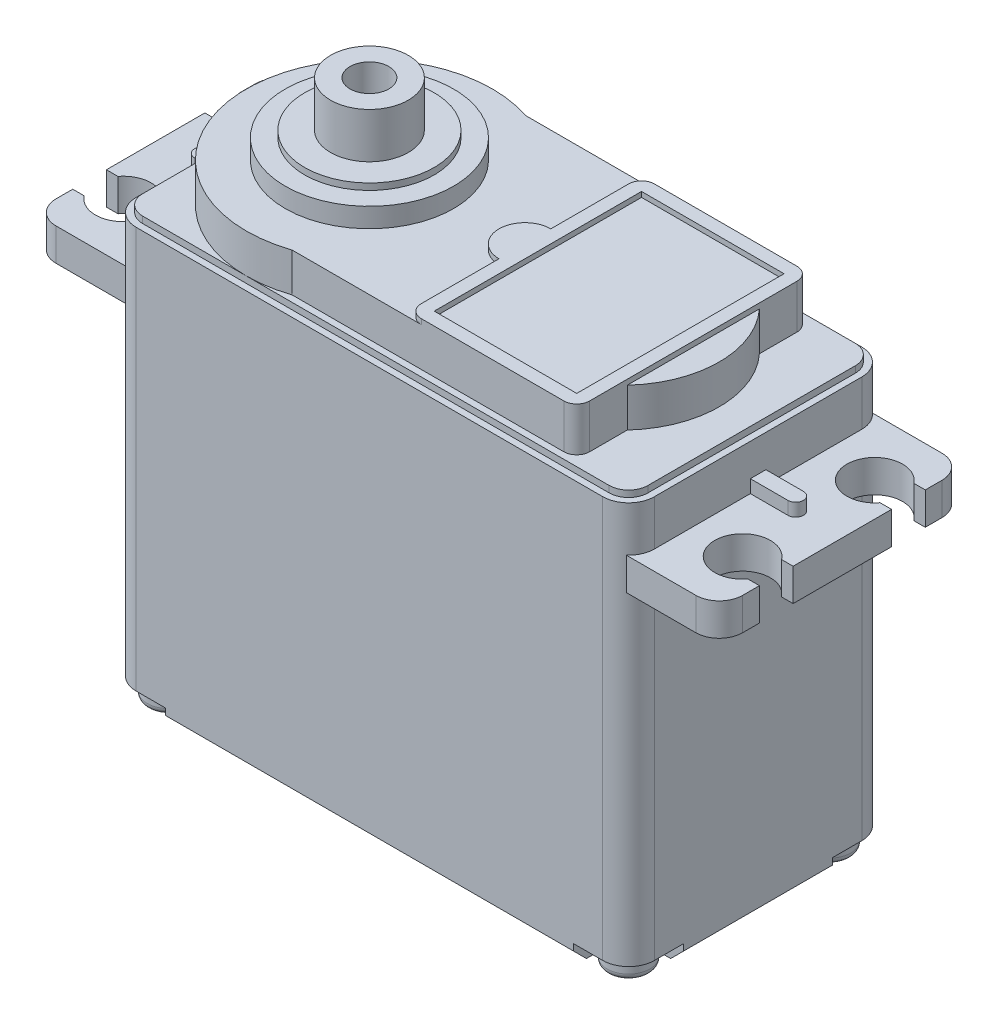
SolidWorks part; units mm, degrees
ref_plane "Спереди" through (0, 0, 0) normal (0, 0, 1) x (1, 0, 0)
ref_plane "Сверху" through (0, 0, 0) normal (0, 1, 0) x (1, 0, 0)
ref_plane "Справа" through (0, 0, 0) normal (1, 0, 0) x (0, 0, -1)
sketch "Эскиз1" plane through (0, 0, 0) normal (0, 1, 0) x (1, 0, 0)
  line L1 (-18, -10) -> (18, -10)
  line L2 (-20, -8) -> (-20, 8)
  line L3 (-18, 10) -> (18, 10)
  line L4 (20, -8) -> (20, 8)
  line L5 (-20, -10) -> (20, 10) construction
  line L6 (-20, 10) -> (20, -10) construction
  arc A0 (-18, -10) -> (-20, -8) centre (-18, -8) cw
  arc A1 (20, -8) -> (18, -10) centre (18, -8) cw
  arc A2 (20, 8) -> (18, 10) centre (18, 8) ccw
  arc A3 (-20, 8) -> (-18, 10) centre (-18, 8) cw
  point P0 (0, 0)
  dimension "D3" = 2
  dimension "D1" = 20
  dimension "D2" = 40
extrude "Бобышка-Вытянуть1" add sketch "Эскиз1" along normal blind 32.5
sketch "Эскиз2" plane through (0, 32.5, 0) normal (0, 1, 0) x (1, 0, 0)
  line L12 (-18, -9.5) -> (18, -9.5)
  line L13 (19.5, -8) -> (19.5, 8)
  line L14 (18, 9.5) -> (-18, 9.5)
  line L15 (-19.5, 8) -> (-19.5, -8)
  line L16 (-18, -9.5) -> (18, -9.5)
  line L17 (19.5, -8) -> (19.5, 8)
  line L18 (18, 9.5) -> (-18, 9.5)
  line L19 (-19.5, 8) -> (-19.5, -8)
  arc A10 (-19.5, -8) -> (-18, -9.5) centre (-18, -8) ccw
  arc A11 (18, -9.5) -> (19.5, -8) centre (18, -8) ccw
  arc A12 (19.5, 8) -> (18, 9.5) centre (18, 8) ccw
  arc A13 (-18, 9.5) -> (-19.5, 8) centre (-18, 8) ccw
  arc A14 (-19.5, -8) -> (-18, -9.5) centre (-18, -8) ccw
  arc A15 (18, -9.5) -> (19.5, -8) centre (18, -8) ccw
  arc A16 (19.5, 8) -> (18, 9.5) centre (18, 8) ccw
  arc A17 (-18, 9.5) -> (-19.5, 8) centre (-18, 8) ccw
  dimension "D1" = 0.5
extrude "Бобышка-Вытянуть2" add sketch "Эскиз2" along normal blind 0.5
sketch "Эскиз3" plane through (0, 0, 0) normal (0, -1, 0) x (1, 0, 0)
  line L0 (-21.9185, 5.75) -> (-17.75, 5.75)
  line L1 (-15.75, 7.75) -> (-15.75, 12.0926)
  line L2 (-20, -8) -> (-20, 8) construction
  line L3 (-18, 10) -> (18, 10) construction
  line L4 (-21.9185, 5.75) -> (-21.9185, 12.0926)
  line L6 (-15.75, 12.0926) -> (-21.9185, 12.0926)
  line L8 (15.75, 12.0926) -> (21.9185, 12.0926)
  line L9 (21.9185, 5.75) -> (21.9185, 12.0926)
  line L10 (15.75, 7.75) -> (15.75, 12.0926)
  line L11 (21.9185, 5.75) -> (17.75, 5.75)
  line L12 (21.9185, -5.75) -> (17.75, -5.75)
  line L13 (15.75, -7.75) -> (15.75, -12.0926)
  line L14 (21.9185, -5.75) -> (21.9185, -12.0926)
  line L15 (15.75, -12.0926) -> (21.9185, -12.0926)
  line L16 (-15.75, -12.0926) -> (-21.9185, -12.0926)
  line L17 (-21.9185, -5.75) -> (-21.9185, -12.0926)
  line L18 (-15.75, -7.75) -> (-15.75, -12.0926)
  line L19 (-21.9185, -5.75) -> (-17.75, -5.75)
  arc A0 (-15.75, 7.75) -> (-17.75, 5.75) centre (-17.75, 7.75) cw
  arc A1 (15.75, 7.75) -> (17.75, 5.75) centre (17.75, 7.75) ccw
  arc A2 (15.75, -7.75) -> (17.75, -5.75) centre (17.75, -7.75) cw
  arc A3 (-15.75, -7.75) -> (-17.75, -5.75) centre (-17.75, -7.75) ccw
  point P11 (-15.75, 5.75)
  point P21 (15.75, 5.75)
  point P34 (15.75, -5.75)
  point P35 (-15.75, -5.75)
  dimension "D3" = 2
  dimension "D1" = 4.25
  dimension "D2" = 4.25
extrude "Вырез-Вытянуть1" cut sketch "Эскиз3" against normal blind 1.5
chamfer "Фаска1" distance 1 angle 45 4 edges at (20, 0, 0) (0, 0, -10) (-20, 0, 0) (0, 0, 10)
sketch "Эскиз4" plane through (0, 33, 0) normal (0, 1, 0) x (1, 0, 0)
  line L1 (18, 9.5) -> (-18, 9.5) construction
  line L2 (-18, -9.5) -> (18, -9.5) construction
  line L3 (-19.5, 8) -> (-19.5, -8) construction
  line L4 (15, 8) -> (15, -8)
  line L5 (20, -8) -> (20, 8) construction
  line L6 (-6.9586, 9) -> (14, 9)
  line L7 (-6.9586, -9) -> (14, -9)
  line L8 (18, 10) -> (-18, 10) construction
  line L9 (-18, -10) -> (18, -10) construction
  arc A0 (-6.9586, 9) -> (-6.9586, -9) centre (-10, 0) ccw
  arc A1 (15, 8) -> (14, 9) centre (14, 8) ccw
  arc A2 (15, -8) -> (14, -9) centre (14, -8) cw
  dimension "D1" = 5
  dimension "D4" = 1
  dimension "D2" = 1
  dimension "D3" = 1
extrude "Бобышка-Вытянуть3" add sketch "Эскиз4" along normal blind 3
sketch "Эскиз5" plane through (0, 36, 0) normal (0, 1, 0) x (1, 0, 0)
  line L0 (15, -8) -> (15, 8) construction
  line L1 (15, -8) -> (15, 8)
  line L2 (2, 8) -> (2, 2)
  line L3 (14, 9) -> (3, 9)
  line L4 (2, -2) -> (2, -8)
  line L5 (14, -9) -> (3, -9)
  line L6 (3, -8) -> (14, -8)
  line L7 (14, 8) -> (3, 8)
  line L8 (3, 8) -> (3, -8)
  line L9 (14, -8) -> (14, 8)
  line L11 (2, 8) -> (2, -8) construction
  arc A0 (15, 8) -> (14, 9) centre (14, 8) ccw construction
  arc A1 (14, -9) -> (15, -8) centre (14, -8) ccw construction
  arc A2 (15, 8) -> (14, 9) centre (14, 8) ccw
  arc A3 (14, -9) -> (15, -8) centre (14, -8) ccw
  arc A4 (3, -9) -> (2, -8) centre (3, -8) cw
  arc A5 (3, 9) -> (2, 8) centre (3, 8) ccw
  arc A6 (2, 2) -> (2, -2) centre (2, 0) ccw
  arc M1 (15, 8) -> (14, 9) centre (14, 8) ccw
  line M2 (14, 9) -> (-6.9586, 9)
  line M4 (-6.9586, -9) -> (14, -9)
  arc M5 (14, -9) -> (15, -8) centre (14, -8) ccw
  line M6 (15, -8) -> (15, 8)
  dimension "D2" = 1
  dimension "D4" = 4
  dimension "D1" = 13
  dimension "D3" = 1
extrude "Бобышка-Вытянуть4" add sketch "Эскиз5" along normal blind 0.4 contours L11 A6 | L2 L11 L4 A4 A5 L9 L6 L8 L7 M4 M5 M6 M1 M2 region at (14.5501, 36, 8.5501) region at (1.1512, 36, 0)
sketch "Эскиз6" plane through (0, 36, 0) normal (0, 1, 0) x (1, 0, 0)
  circle A0 centre (-10, 0) radius 6.5
  dimension "D1" = 13
extrude "Бобышка-Вытянуть5" add sketch "Эскиз6" along normal blind 1.5
sketch "Эскиз7" plane through (0, 37.5, 0) normal (0, 1, 0) x (1, 0, 0)
  circle A0 centre (-10, 0) radius 5
  dimension "D1" = 10
extrude "Бобышка-Вытянуть6" add sketch "Эскиз7" along normal blind 0.5
sketch "Эскиз8" plane through (0, 38, 0) normal (0, 1, 0) x (1, 0, 0)
  circle A0 centre (-10, 0) radius 3
  circle A1 centre (-10, 0) radius 1.5
  dimension "D1" = 6
  dimension "D2" = 3
extrude "Бобышка-Вытянуть7" add sketch "Эскиз8" along normal blind 3.5
sketch "Эскиз9" plane through (0, 33, 0) normal (0, 1, 0) x (1, 0, 0)
  line L1 (20, -8) -> (20, 8) construction
  line L2 (14.5, 5.5902) -> (14.5, -5.5902)
  line L3 (19.5, -8) -> (19.5, 8) construction
  arc A0 (14.5, -5.5902) -> (14.5, 5.5902) centre (9.5, 0) ccw
  dimension "D1" = 15
  dimension "D2" = 10.5
  dimension "D3" = 5
extrude "Бобышка-Вытянуть8" add sketch "Эскиз9" along normal blind 3
ref_plane "Плоскость1" through (0, 26.5, 0) normal (0, -1, 0) x (-1, 0, 0)
sketch "Эскиз10" plane through (0, 26.5, 0) normal (0, -1, 0) x (-1, 0, 0)
  line L0 (-26.5, 6.4) -> (-25.6125, 6.4)
  line L1 (-24.6884, -9.5) -> (24.6884, -9.5)
  line L2 (-26.5, -7.6884) -> (-26.5, -6.4)
  line L3 (-24.6884, 9.5) -> (24.6884, 9.5)
  line L4 (26.5, -7.6884) -> (26.5, -6.4)
  line L5 (-26.5, -9.5) -> (26.5, 9.5) construction
  line L6 (-26.5, 9.5) -> (26.5, -9.5) construction
  line L7 (-26.5, 3.8) -> (-25.6125, 3.8)
  line L8 (-26.5, 6.4) -> (-26.5, 7.6884)
  line L9 (0, 0) -> (-7.7074, 0) construction
  line L10 (-7.7074, 0) -> (0, 0) construction
  line L11 (0, 0) -> (0, 4.5311) construction
  line L12 (26.5, 3.8) -> (25.6125, 3.8)
  line L13 (26.5, 6.4) -> (25.6125, 6.4)
  line L14 (26.5, 6.4) -> (26.5, 7.6884)
  line L15 (26.5, -3.8) -> (25.6125, -3.8)
  line L16 (26.5, -6.4) -> (25.6125, -6.4)
  line L17 (-26.5, -3.8) -> (-25.6125, -3.8)
  line L18 (-26.5, -6.4) -> (-25.6125, -6.4)
  line L19 (26.5, -3.8) -> (26.5, 3.8)
  line L20 (-26.5, -3.8) -> (-26.5, 3.8)
  arc A0 (26.5, 7.6884) -> (24.6884, 9.5) centre (24.6884, 7.6884) ccw
  arc A1 (26.5, -7.6884) -> (24.6884, -9.5) centre (24.6884, -7.6884) cw
  arc A2 (-24.6884, -9.5) -> (-26.5, -7.6884) centre (-24.6884, -7.6884) cw
  arc A3 (-26.5, 7.6884) -> (-24.6884, 9.5) centre (-24.6884, 7.6884) cw
  arc A4 (-25.6125, 3.8) -> (-25.6125, 6.4) centre (-23.9, 5.1) ccw
  arc A5 (25.6125, 3.8) -> (25.6125, 6.4) centre (23.9, 5.1) cw
  arc A6 (25.6125, -3.8) -> (25.6125, -6.4) centre (23.9, -5.1) ccw
  arc A7 (-25.6125, -3.8) -> (-25.6125, -6.4) centre (-23.9, -5.1) cw
  point P0 (0, 0)
  dimension "D3" = 1.8116
  dimension "D4" = 4.3
  dimension "D1" = 19
  dimension "D2" = 53
  dimension "D5" = 5.1
  dimension "D6" = 23.9
  dimension "D7" = 1.3
  dimension "D8" = 2.6
extrude "Бобышка-Вытянуть9" add sketch "Эскиз10" against normal blind 2.5
sketch "Эскиз11" plane through (0, 29, 0) normal (0, 1, 0) x (1, 0, 0)
  line L0 (26.5, 3.8) -> (26.5, -3.8) construction
  line L1 (22.9, 0.6) -> (18.0276, 0.6)
  line L2 (22.9, -0.6) -> (18.0276, -0.6)
  line L6 (18.0276, -0.6) -> (18.0276, 0.6)
  line L7 (0, 0) -> (0, 3.7247) construction
  line L8 (-22.9, 0.6) -> (-18.0276, 0.6)
  line L9 (-18.0276, -0.6) -> (-18.0276, 0.6)
  line L10 (-22.9, -0.6) -> (-18.0276, -0.6)
  arc A0 (22.9, -0.6) -> (22.9, 0.6) centre (22.9, 0) ccw
  arc A1 (2, 2) -> (2, -2) centre (2, 0) ccw construction
  arc A2 (-22.9, -0.6) -> (-22.9, 0.6) centre (-22.9, 0) cw
  point P4 (26.5, 0)
  dimension "D1" = 1.2
  dimension "D2" = 3.6
extrude "Бобышка-Вытянуть10" add sketch "Эскиз11" along normal blind 1
sketch "Эскиз12" plane through (0, 1.5, 0) normal (0, -1, 0) x (1, 0, 0)
  line L0 (0, 0) -> (0, 4.3916) construction
  line L1 (0, 0) -> (-4.3775, 0) construction
  line L2 (-18, 8) -> (-19, 8)
  line L3 (-19, 8) -> (-19, 7.5)
  line L4 (-19, 7.5) -> (-18, 7.5)
  line L5 (-17.5, 8) -> (-17.5, 9)
  line L6 (-17.5, 9) -> (-18, 9)
  line L7 (-18, 9) -> (-18, 8)
  line L8 (-17.5, 7.5) -> (-16.5, 7.5)
  line L9 (-16.5, 7.5) -> (-16.5, 8)
  line L10 (-16.5, 8) -> (-17.5, 8)
  line L11 (-18, 7.5) -> (-18, 6.5)
  line L12 (-18, 6.5) -> (-17.5, 6.5)
  line L13 (-17.5, 6.5) -> (-17.5, 7.5)
  line L14 (16.5, 7.5) -> (16.5, 8)
  line L15 (17.5, 7.5) -> (16.5, 7.5)
  line L16 (17.5, 6.5) -> (17.5, 7.5)
  line L17 (18, 6.5) -> (17.5, 6.5)
  line L18 (18, 7.5) -> (18, 6.5)
  line L19 (19, 7.5) -> (18, 7.5)
  line L20 (19, 8) -> (19, 7.5)
  line L21 (18, 8) -> (19, 8)
  line L22 (18, 9) -> (18, 8)
  line L23 (17.5, 9) -> (18, 9)
  line L24 (17.5, 8) -> (17.5, 9)
  line L25 (16.5, 8) -> (17.5, 8)
  line L26 (16.5, -8) -> (17.5, -8)
  line L27 (16.5, -7.5) -> (16.5, -8)
  line L28 (17.5, -7.5) -> (16.5, -7.5)
  line L29 (18, -6.5) -> (17.5, -6.5)
  line L30 (17.5, -6.5) -> (17.5, -7.5)
  line L31 (18, -7.5) -> (18, -6.5)
  line L32 (19, -7.5) -> (18, -7.5)
  line L33 (19, -8) -> (19, -7.5)
  line L34 (18, -8) -> (19, -8)
  line L35 (18, -9) -> (18, -8)
  line L36 (17.5, -9) -> (18, -9)
  line L37 (17.5, -8) -> (17.5, -9)
  line L38 (-17.5, -6.5) -> (-17.5, -7.5)
  line L39 (-18, -6.5) -> (-17.5, -6.5)
  line L40 (-18, -7.5) -> (-18, -6.5)
  line L41 (-19, -7.5) -> (-18, -7.5)
  line L42 (-19, -8) -> (-19, -7.5)
  line L43 (-18, -8) -> (-19, -8)
  line L44 (-16.5, -7.5) -> (-16.5, -8)
  line L45 (-17.5, -7.5) -> (-16.5, -7.5)
  line L46 (-16.5, -8) -> (-17.5, -8)
  line L47 (-17.5, -8) -> (-17.5, -9)
  line L48 (-18, -9) -> (-18, -8)
  line L49 (-17.5, -9) -> (-18, -9)
  circle A0 centre (-17.75, 7.75) radius 1.65
  circle A1 centre (17.75, 7.75) radius 1.65
  circle A2 centre (17.75, -7.75) radius 1.65
  circle A3 centre (-17.75, -7.75) radius 1.65
  dimension "D1" = 3.3
  dimension "D2" = 7.75
  dimension "D3" = 17.75
  dimension "D4" = 0.5
  dimension "D5" = 0.25
  dimension "D6" = 1.25
  dimension "D7" = 4
extrude "Бобышка-Вытянуть11" add sketch "Эскиз12" along normal blind 1.5
fillet "Скругление1" radius 0.5 4 edges at (17.75, 0, 9.4) (17.75, 0, -9.4) (-17.75, 0, -6.1) (-17.75, 0, 6.1)
